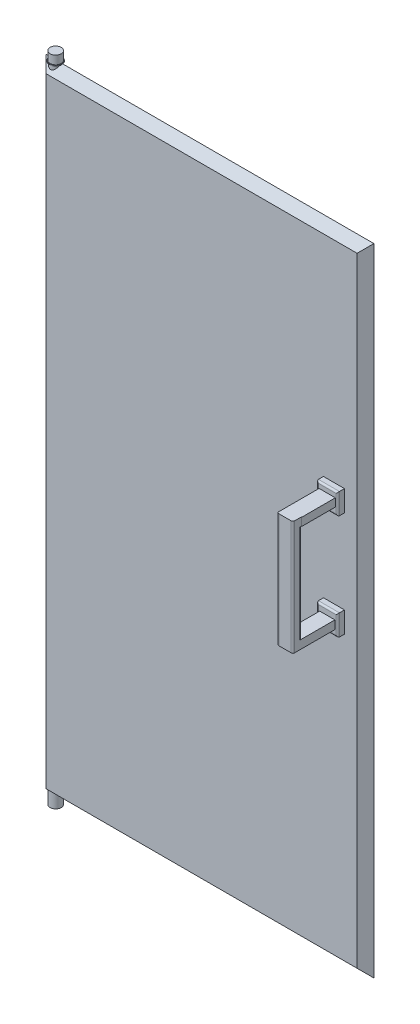
SolidWorks part; units mm, degrees
ref_plane "Front Plane" through (0, 0, 0) normal (0, 0, 1) x (1, 0, 0)
ref_plane "Top Plane" through (0, 0, 0) normal (0, 1, 0) x (1, 0, 0)
ref_plane "Right Plane" through (0, 0, 0) normal (1, 0, 0) x (0, 0, -1)
sketch "Sketch1" plane through (0, 0, 0) normal (0, 0, 1) x (1, 0, 0)
  line L0 (-40.5907, 32.0721) -> (349.4093, 32.0721)
  line L1 (349.4093, 32.0721) -> (349.4093, -724.7279)
  line L2 (349.4093, -724.7279) -> (-40.5907, -724.7279)
  line L3 (-40.5907, -724.7279) -> (-40.5907, 32.0721)
extrude "Boss-Extrude1" add sketch "Sketch1" along normal blind 20
sketch "Sketch2" plane through (0, 32.0721, 0) normal (0, 1, 0) x (1, 0, 0)
  circle A0 centre (-28.7838, -10.4351) radius 6.05
extrude "Boss-Extrude2" add sketch "Sketch2" along normal blind 10
sketch "Sketch3" plane through (0, -724.7279, 0) normal (0, -1, 0) x (1, 0, 0)
  circle A0 centre (-28.7838, 10.4351) radius 6.631
extrude "Boss-Extrude3" add sketch "Sketch3" along normal blind 10
chamfer "Chamfer1" distance 10 angle 45 8 edges at (-40.5907, -346.3279, 20) (154.4093, -724.7279, 20) (349.4093, -346.3279, 20) (154.4093, 32.0721, 20) (-40.5907, -346.3279, 0) (154.4093, -724.7279, 0) (349.4093, -346.3279, 0) (154.4093, 32.0721, 0)
sketch "Sketch4" plane through (0, 0, 20) normal (0, 0, 1) x (1, 0, 0)
  line L0 (339.4093, 22.0721) -> (339.4093, -346.3279)
  line L1 (339.4093, -714.7279) -> (339.4093, 22.0721) construction
  line L3 (309.4093, -346.3279) -> (309.4093, -246.3279)
  line L4 (309.4093, -246.3279) -> (339.4093, -246.3279)
  line L5 (339.4093, -246.3279) -> (339.4093, -446.3279)
  line L6 (339.4093, -446.3279) -> (309.4093, -446.3279)
  line L7 (309.4093, -446.3279) -> (309.4093, -346.3279)
extrude "Boss-Extrude5" add sketch "Sketch4" along normal blind 50 contours L7 L6 L4 L3 region at (324.4093, -346.3279, 20)
sketch "Sketch5" plane through (339.4093, 0, 0) normal (1, 0, 0) x (0, 0, -1)
  line L0 (-20, -246.3279) -> (-20, -266.3279)
  line L1 (-20, -446.3279) -> (-20, -246.3279) construction
  line L2 (-20, -266.3279) -> (-50, -266.3279)
  line L3 (-50, -266.3279) -> (-50, -426.3279)
  line L4 (-50, -426.3279) -> (-20, -426.3279)
  line L5 (-20, -426.3279) -> (-20, -266.3279)
  line M1 (-20, -446.3279) -> (-20, -246.3279)
extrude "Cut-Extrude1" cut sketch "Sketch5" against normal blind 50 contours L3 L4 L2 M1 region at (339.4093, -346.3279, 35)
chamfer "Chamfer2" distance 10 angle 45 8 edges at (324.4093, -246.3279, 70) (339.4093, -246.3279, 45) (339.4093, -346.3279, 70) (339.4093, -446.3279, 45) (324.4093, -446.3279, 70) (309.4093, -446.3279, 45) (309.4093, -346.3279, 70) (309.4093, -246.3279, 45)
sketch "Sketch7" plane through (0, 0, 20) normal (0, 0, 1) x (1, 0, 0)
  line L0 (309.4093, -256.3279) -> (319.4093, -246.3279)
  line L1 (319.4093, -246.3279) -> (329.4093, -246.3279)
  line L2 (329.4093, -246.3279) -> (339.4093, -256.3279)
  line L3 (339.4093, -256.3279) -> (339.4093, -436.3279)
  line L4 (339.4093, -436.3279) -> (329.4093, -446.3279)
  line L5 (329.4093, -446.3279) -> (319.4093, -446.3279)
  line L6 (319.4093, -446.3279) -> (309.4093, -436.3279)
  line L7 (309.4093, -436.3279) -> (309.4093, -256.3279)
extrude "Cut-Extrude2" cut sketch "Sketch7" along normal blind 121
sketch "Sketch10" plane through (0, 0, 20) normal (0, 0, 1) x (1, 0, 0)
  line L0 (339.4093, -714.7279) -> (339.4093, 22.0721) construction
  line L1 (299.4093, -227.9279) -> (324.4093, -227.9279)
  line L2 (299.4093, -227.9279) -> (299.4093, -252.9279)
  line L3 (299.4093, -252.9279) -> (324.4093, -252.9279)
  line L4 (324.4093, -227.9279) -> (324.4093, -252.9279)
  line L5 (299.4093, -352.9279) -> (324.4093, -352.9279)
  line L6 (299.4093, -352.9279) -> (299.4093, -377.9279)
  line L7 (299.4093, -377.9279) -> (324.4093, -377.9279)
  line L8 (324.4093, -352.9279) -> (324.4093, -377.9279)
  line L9 (339.4093, 22.0721) -> (-30.5907, 22.0721) construction
  dimension "D1" = 25
  dimension "D2" = 25
  dimension "D3" = 25
  dimension "D4" = 25
  dimension "D5" = 15
  dimension "D6" = 15
  dimension "D7" = 100
  dimension "D8" = 250
extrude "Boss-Extrude7" add sketch "Sketch10" along normal blind 8
sketch "Sketch15" plane through (0, 0, 28) normal (0, 0, 1) x (1, 0, 0)
  line L1 (302.2245, -234.8471) -> (321.5457, -234.8471)
  line L2 (302.2245, -234.8471) -> (302.2245, -244.3716)
  line L3 (302.2245, -244.3716) -> (321.5457, -244.3716)
  line L4 (321.5457, -234.8471) -> (321.5457, -244.3716)
extrude "Boss-Extrude8" add sketch "Sketch15" along normal blind 40
sketch "Sketch16" plane through (0, 0, 28) normal (0, 0, 1) x (1, 0, 0)
  line L1 (302.9521, -360.896) -> (321.0374, -360.896)
  line L2 (302.9521, -360.896) -> (302.9521, -370.8905)
  line L3 (302.9521, -370.8905) -> (321.0374, -370.8905)
  line L4 (321.0374, -360.896) -> (321.0374, -370.8905)
extrude "Boss-Extrude9" add sketch "Sketch16" along normal blind 40
sketch "Sketch18" plane through (0, 0, 68) normal (0, 0, 1) x (1, 0, 0)
  line L1 (302.2245, -234.8471) -> (321.0374, -234.8471)
  line L2 (302.2245, -234.8471) -> (302.2245, -370.8905)
  line L3 (302.2245, -370.8905) -> (321.0374, -370.8905)
  line L4 (321.0374, -234.8471) -> (321.0374, -370.8905)
extrude "Boss-Extrude10" add sketch "Sketch18" along normal blind 10
fillet "Fillet1" radius 2 4 edges at (302.2245, -307.6311, 68) (321.0374, -302.6338, 68) (321.0374, -302.8688, 78) (302.2245, -302.8688, 78)
fillet "Fillet2" radius 2 4 edges at (299.4093, -240.4279, 28) (311.9093, -252.9279, 28) (324.4093, -240.4279, 28) (311.9093, -227.9279, 28)
fillet "Fillet3" radius 2 4 edges at (299.4093, -365.4279, 28) (311.9093, -377.9279, 28) (324.4093, -365.4279, 28) (311.9093, -352.9279, 28)
sketch "Sketch23" plane through (0, 42.0721, 0) normal (0, 1, 0) x (1, 0, 0)
  circle A0 centre (-28.7838, -10.4351) radius 6.05
extrude "Cut-Extrude3" cut sketch "Sketch23" against normal blind 10
sketch "Sketch24" plane through (0, 32.0721, 0) normal (0, 1, 0) x (1, 0, 0)
  circle A0 centre (-28.7838, -10.4351) radius 7.2999
extrude "Boss-Extrude11" add sketch "Sketch24" against normal blind 1
sketch "Sketch27" plane through (0, 32.0721, 0) normal (0, 1, 0) x (1, 0, 0)
  circle A0 centre (-28.7838, -10.4351) radius 6.631
  dimension "D1" = 13.2621
extrude "Boss-Extrude12" add sketch "Sketch27" along normal blind 10
